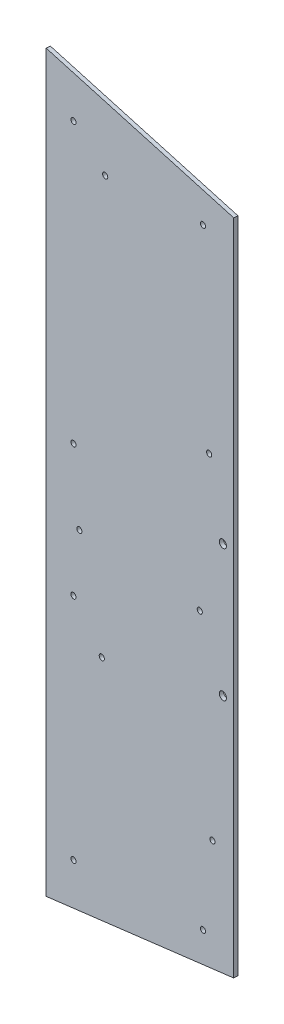
SolidWorks part; units mm, degrees
material "6061-T6 (SS)"
ref_plane "X-Y Datum" through (0, 0, 0) normal (0, 0, 1) x (1, 0, 0)
ref_plane "X-Z Datum" through (0, 0, 0) normal (0, 1, 0) x (1, 0, 0)
ref_plane "Y-Z Datum" through (0, 0, 0) normal (1, 0, 0) x (0, 0, -1)
ref_plane "Plane1" through (1.0099, 0, -13.5995) normal (0.0741, 0, -0.9973) x (-0.9973, 0, -0.0741)
ref_plane "Plane2" through (1.9503, 0, -26.2646) normal (0.0741, 0, -0.9973) x (-0.9973, 0, -0.0741)
sketch "Sketch1" plane through (1.9503, 0, -26.2646) normal (0.0741, 0, -0.9973) x (-0.9973, 0, -0.0741)
  line L0 (-183.6444, -298.45) -> (-183.6444, 298.45) construction
  line L1 (-183.6444, -298.45) -> (-826.7602, -177.8) construction
  line L2 (-826.7602, -177.8) -> (-826.7602, 177.8) construction
  line L3 (-826.7602, 177.8) -> (-183.6444, 298.45) construction
  line L4 (-183.6444, -298.45) -> (-183.6444, 298.45)
  line L5 (-183.6444, -298.45) -> (-826.7602, -177.8)
  line L6 (-826.7602, -177.8) -> (-826.7602, 177.8)
  line L7 (-826.7602, 177.8) -> (-183.6444, 298.45)
extrude "Boss-Extrude1" add sketch "Sketch1" along normal blind 3.175
ref_plane "Plane3" through (1.9503, 0, -26.2646) normal (-0.0741, 0, 0.9973) x (0.9973, 0, 0.0741)
sketch "Sketch2" plane through (1.9503, 0, -26.2646) normal (-0.0741, 0, 0.9973) x (0.9973, 0, 0.0741)
  circle A0 centre (0, 0) radius 14.2875
  dimension "D1" = 28.575
extrude "Cut-Extrude1" [suppressed] cut sketch "Sketch2" against normal through all contours A0
mirror "Mirror1" [suppressed] about plane through (0, 0, 0) normal (0, 1, 0)
sketch "Sketch3" plane through (1.9503, 0, -26.2646) normal (-0.0741, 0, 0.9973) x (0.9973, 0, 0.0741)
  line L0 (183.6444, 0) -> (826.7602, 0) construction
  line L1 (183.6444, -298.45) -> (183.6444, 298.45) construction
  line L2 (826.7602, 177.8) -> (826.7602, -177.8) construction
  line L3 (348.7444, 267.4769) -> (348.7444, -267.4769)
  line L4 (826.7602, -177.8) -> (183.6444, -298.45) construction
  point P11 (348.7444, 0)
  line M3 (183.6444, -298.45) -> (826.7602, -177.8)
  line M5 (826.7602, -177.8) -> (826.7602, 177.8)
  line M7 (826.7602, 177.8) -> (183.6444, 298.45)
  dimension "D1" = 165.1
extrude "Cut-Extrude2" cut sketch "Sketch3" against normal through all contours L0 L3 M3 M5 | L3 L0 M5 M7 region at (572.0878, 112.8243, 16.0723) region at (572.0878, -112.8243, 16.0723)
sketch "Sketch4" plane through (2.1855, 0, -29.4309) normal (0.0741, 0, -0.9973) x (-0.9973, 0, -0.0741)
  point P0 (-321.7191, 248.0519)
  point P1 (-207.7194, 260)
  point P2 (-207.7194, 260)
  point P3 (-207.7194, 33)
  point P4 (-207.7194, -260)
  point P5 (-207.7194, -74)
  point P6 (-207.7194, -74)
  point P7 (-321.7191, -248.0519)
  point P8 (-330.0069, -180.725)
  point P9 (-330.0069, -180.725)
  point P10 (-232.6444, -104)
  point P11 (-318.8944, -25)
  point P12 (-318.8944, -25)
  point P13 (-212.8944, -25)
  point P14 (-212.8944, -25)
  point P15 (-235.6444, 236.6)
  point P16 (-235.6444, 236.6)
  point P17 (-327.1444, 90)
hole_wizard "M4 Clearance Hole1" positions "Sketch4" profile "Sketch5" hole size "M4" standard "ANSI Metric" end condition through all
sketch "Sketch5" plane through (323.0212, 248.0519, -5.6065) normal (0, 1, 0) x (-0.9973, 0, -0.0741)
  line L0 (0, 0) -> (0, 15.3677)
  line L1 (0, 15.3677) -> (2.25, 15.3677)
  line L2 (2.25, 15.3677) -> (2.25, 0)
  line L5 (2.25, 0) -> (0, 0)
  line L11 (0, -6.35) -> (0, 107.95) construction
  dimension "Thru Hole Dia." = 4.5
  dimension "Thru Hole Depth" = 15.3677
sketch "Sketch6" plane through (1.9503, 0, -26.2646) normal (-0.0741, 0, 0.9973) x (0.9973, 0, 0.0741)
  line L0 (207.7194, 33) -> (348.7444, 33) construction
  line L1 (348.7444, 267.4769) -> (348.7444, -267.4769) construction
  line L2 (207.7194, -74) -> (348.7444, -74) construction
  circle A0 centre (339.2194, 33) radius 3.175
  circle A1 centre (339.2194, -74) radius 3.175
  dimension "D1" = 6.35
  dimension "D2" = 9.525
extrude "Cut-Extrude3" cut sketch "Sketch6" against normal through all
